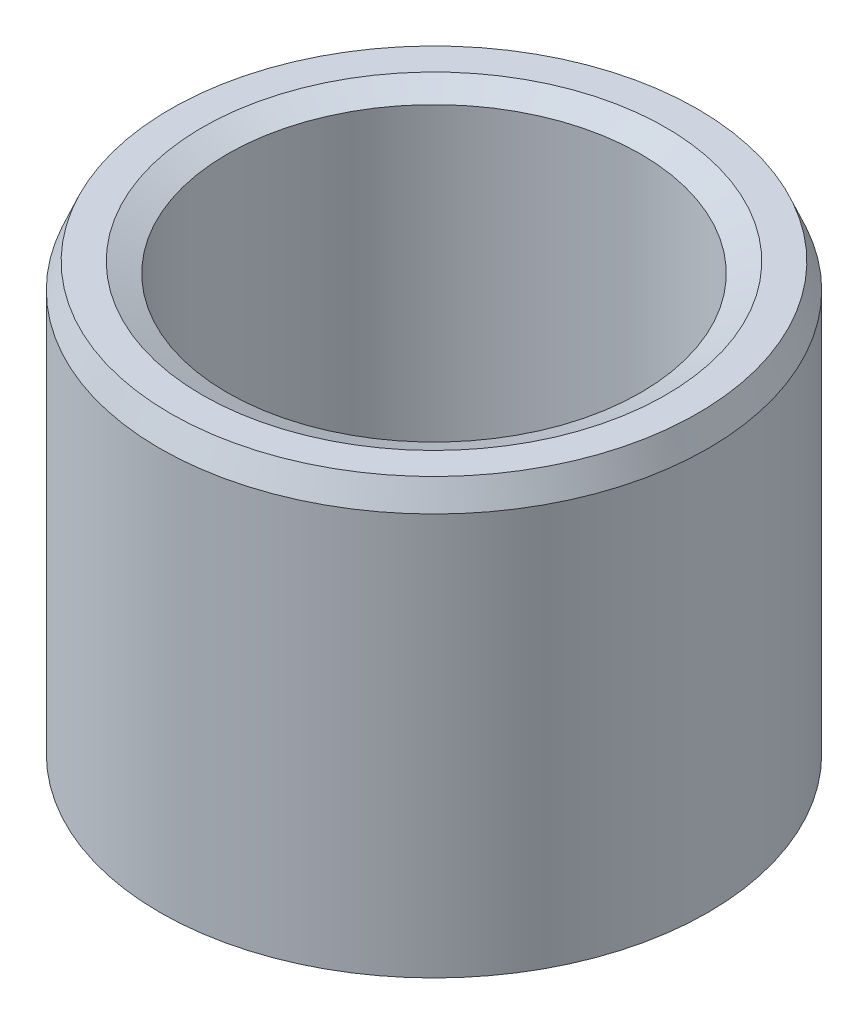
SolidWorks part; units mm, degrees
ref_plane "Front Plane" through (0, 0, 0) normal (0, 0, 1) x (1, 0, 0)
ref_plane "Top Plane" through (0, 0, 0) normal (0, 1, 0) x (1, 0, 0)
ref_plane "Right Plane" through (0, 0, 0) normal (1, 0, 0) x (0, 0, -1)
sketch "Sketch1" plane through (0, 0, 0) normal (0, 1, 0) x (1, 0, 0)
  circle A0 centre (0, 0) radius 15
  dimension "SLEEVE_OD" = 30
extrude "Boss-Extrude1" add sketch "Sketch1" along normal blind 23.9304
sketch "Sketch2" plane through (0, 0, 0) normal (0, 1, 0) x (1, 0, 0)
  circle A0 centre (0, 0) radius 11.3082
  dimension "BORE_D" = 22.6163
extrude "Cut-Extrude1" cut sketch "Sketch2" along normal through all
chamfer "Chamfer1" distance 1.3725 angle 22.71 4 edges at (0, 23.9304, 11.3082) (0, 0, 11.3082) (0, 0, 15) (0, 23.9304, 15) first distance on face at (0, 23.9304, 11.3082) first distance on face at (0, 0, 11.3082) first distance on face at (0, 23.9304, 15)
